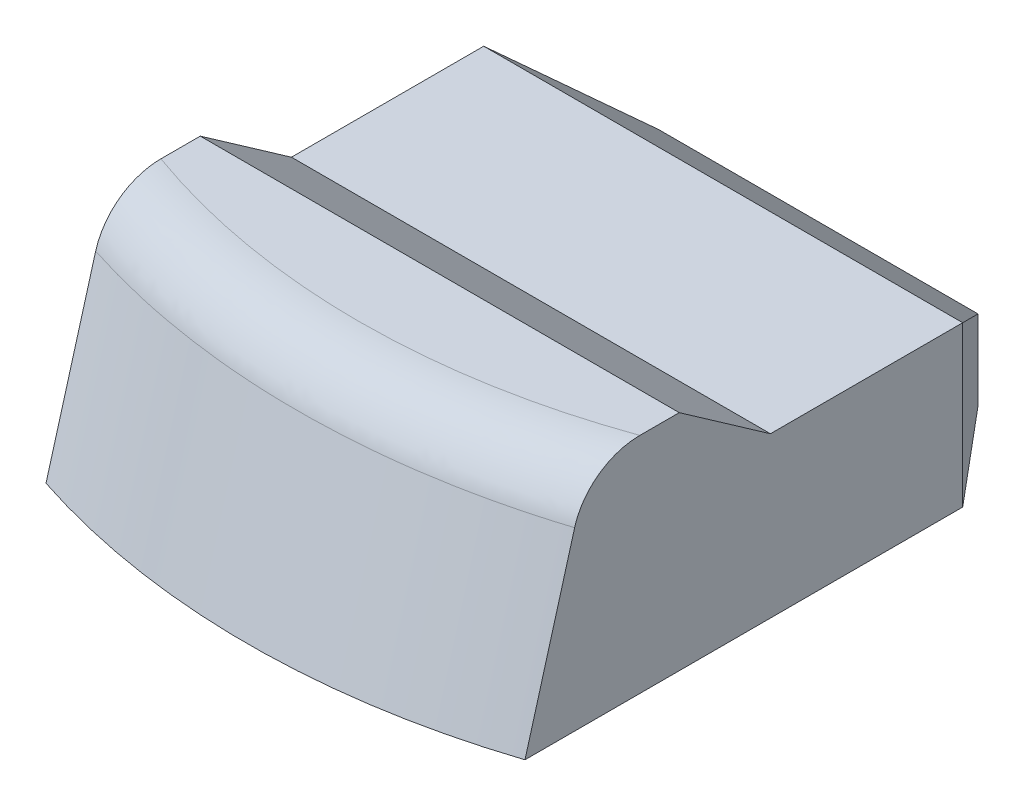
SolidWorks part; units mm, degrees
ref_plane "前视基准面" through (0, 0, 0) normal (0, 0, 1) x (1, 0, 0)
ref_plane "上视基准面" through (0, 0, 0) normal (0, 1, 0) x (1, 0, 0)
ref_plane "右视基准面" through (0, 0, 0) normal (1, 0, 0) x (0, 0, -1)
sketch "草图1" plane through (0, 0, 0) normal (0, 1, 0) x (1, 0, 0)
  line L5 (-1.5, 1) -> (1.5, 1)
  line L6 (-1.5, 1) -> (-1.5, -2.8)
  line L7 (-1.5, -2.8) -> (1.5, -2.8)
  line L8 (1.5, 1) -> (1.5, -2.8)
  point P4 (0, 1)
  dimension "D1" = 3
  dimension "D2" = 1
  dimension "D3" = 3.8
extrude "凸台-拉伸1" add sketch "草图1" along normal blind 1
sketch "草图2" plane through (0, 1, 0) normal (0, 1, 0) x (1, 0, 0)
  line L0 (1.5, -2.8) -> (1.5, 1) construction
  line L1 (-1.5, -2.8) -> (1.5, -2.8)
  line L2 (-1.5, -2.8) -> (-1.5, -0.8)
  line L3 (-1.5, -0.8) -> (1.5, -0.8)
  line L4 (1.5, -2.8) -> (1.5, -0.8)
  dimension "D1" = 2
extrude "凸台-拉伸2" add sketch "草图2" along normal blind 1
chamfer "倒角1" distance 0.5 angle 50 3 edges at (1.5, 0.5, -1) (-1.5, 0.5, -1) (0, 1, -1) first distance on face at (0, 0.5, -1)
sketch "草图3" plane through (0, 0, 2.8) normal (0, 0, 1) x (1, 0, 0)
  line L0 (-0.75, 1) -> (0.75, 1) construction
  line L1 (-0.75, 2) -> (0.75, 2)
  line L2 (-0.75, 0) -> (0.75, 0)
  line L3 (-1.5, 2) -> (1.5, 2) construction
  line L4 (-1.5, 0) -> (1.5, 0) construction
  line L5 (0, 1) -> (0, 0) construction
  arc A0 (-0.75, 2) -> (-0.75, 0) centre (-0.75, 1) ccw
  arc A1 (0.75, 0) -> (0.75, 2) centre (0.75, 1) ccw
  point P2 (0, 1)
  dimension "D1" = 1.5
chamfer "倒角3" distance 1 angle 55 1 edges at (0, 2, 0.8) first distance on face at (0, 1.5, 0.8)
sketch "草图4" plane through (0, 0, 0) normal (0, -1, 0) x (1, 0, 0)
  line L0 (1.6, 2.3034) -> (2.0905, 2.7939)
  line L1 (2.0905, 2.7939) -> (1.7359, 4.0872)
  line L2 (1.7359, 4.0872) -> (1.7194, 4.0898)
  line L3 (1.7194, 4.0898) -> (-1.6729, 4.0898)
  line L4 (-1.6729, 4.0898) -> (-1.9105, 3.4862)
  line L5 (-1.9105, 3.4862) -> (-2.191, 2.5703)
  line L6 (-2.191, 2.5703) -> (-1.6, 2.3034)
  arc A1 (1.6, 2.3034) -> (-1.6, 2.3034) centre (0, -2.2336) ccw
sketch "草图6" plane through (1.5, 0, 0) normal (1, 0, 0) x (0, 0, -1)
  line L0 (-2.5703, 0) -> (-2.0085, 1.9932) construction
  line L1 (-2.5703, 0) -> (-2.3034, 0) construction
extrude "切除-拉伸1" cut sketch "草图4" along direction (0, 0.9625, -0.2713) on the side against the normal blind 3.4 contours L4 L5 L6 A1 L0 L1 L2 L3
sketch "草图7" plane through (0, 1, 0) normal (0, 1, 0) x (1, 0, 0)
  line L1 (2.7164, -3.5324) -> (-2.6987, -3.5324)
  line L2 (2.7164, -3.5324) -> (2.7164, 0.3027)
  line L3 (2.7164, 0.3027) -> (-2.6987, 0.3027)
  line L4 (-2.6987, -3.5324) -> (-2.6987, 0.3027)
extrude "切除-拉伸2" cut sketch "草图7" along normal blind 3.4 from offset 0.4
fillet "圆角1" radius 0.4 1 edges at (-0.0743, 1.4, 2.1821)
